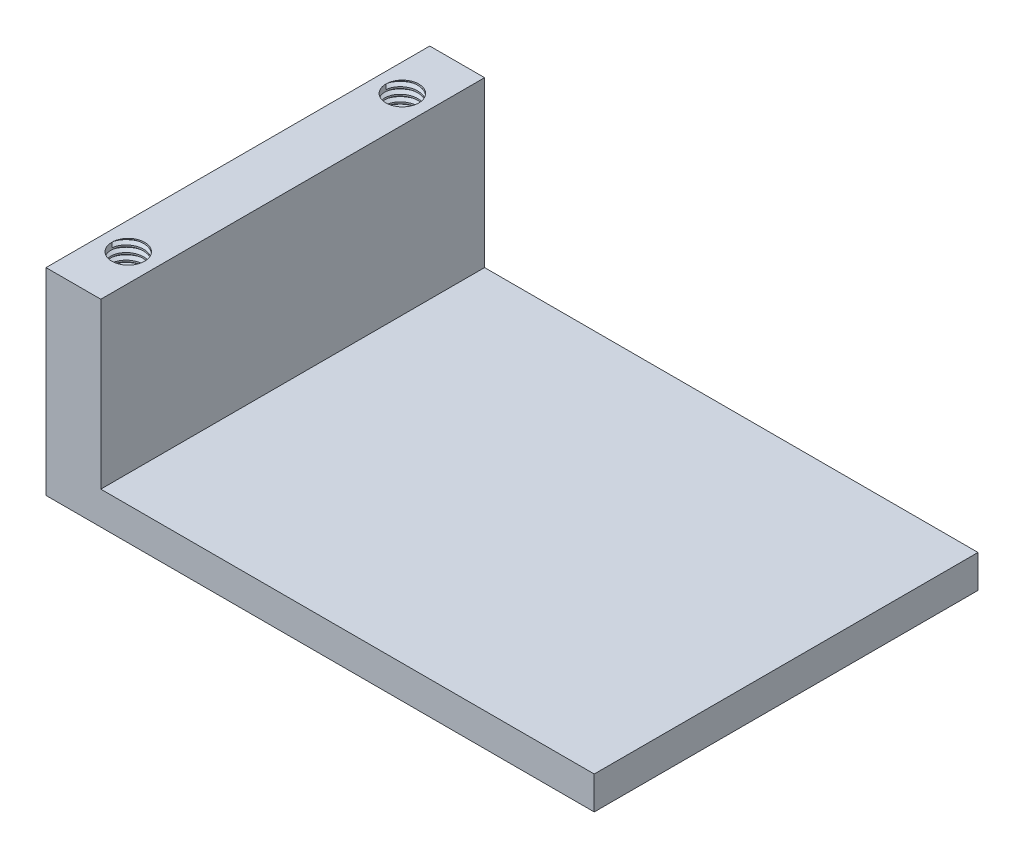
SolidWorks part; units mm, degrees
ref_plane "Front Plane" through (0, 0, 0) normal (0, 0, 1) x (1, 0, 0)
ref_plane "Top Plane" through (0, 0, 0) normal (0, 1, 0) x (1, 0, 0)
ref_plane "Right Plane" through (0, 0, 0) normal (1, 0, 0) x (0, 0, -1)
sketch "Sketch1" plane through (0, 0, 0) normal (0, 0, 1) x (1, 0, 0)
  line L1 (0, 0) -> (4, 0)
  line L2 (0, 0) -> (0, 18)
  line L3 (0, 18) -> (5, 18)
  line L4 (5, 3) -> (5, 18)
  line L5 (4, 0) -> (50, 0)
  line L7 (5, 3) -> (50, 3)
  line L8 (50, 0) -> (50, 3)
  dimension "D1" = 5
  dimension "D2" = 18
  dimension "D3" = 3
  dimension "D4" = 50
extrude "Boss-Extrude1" add sketch "Sketch1" along normal blind 35
sketch "Sketch2" plane through (0, 18, 0) normal (0, 1, 0) x (1, 0, 0)
  circle A0 centre (2.5, -5) radius 1.5
  circle A1 centre (2.5, -30) radius 1.5
extrude "Cut-Extrude1" cut sketch "Sketch2" against normal blind 9
thread "Thread1" pitch 0.6 method cut profile "Thread Profile1" start angle 0, offset 0, length 10, pitch 0.6, diameter 3
ref_plane "Plane1" through (1, 18, 30) normal (0, 0, 1) x (-1, 0, 0)
sketch "Thread Profile1" plane through (1, 18, 30) normal (0, 0, 1) x (-1, 0, 0)
  line L0 (0, 0) -> (0, 0.6) construction
  line L1 (0, 0) -> (0.3248, 0.1875)
  line L2 (0.3248, 0.1875) -> (0.3248, 0.2625)
  line L3 (0.3248, 0.2625) -> (0, 0.45)
  line L4 (0.3248, 0.225) -> (0, 0.225) construction
  line L11 (0, 0) -> (0, 0.45)
  point P2 (0, 0)
  dimension "Pitch" = 0.6
  dimension "Profile_Angle" = 60
  dimension "Profile_Land" = 0.075
  dimension "Profile_Height" = 0.3248
thread "Thread2" pitch 0.6 method cut profile "Thread Profile2" start angle 0, offset 0, length 10, pitch 0.6, diameter 3
ref_plane "Plane2" through (1, 18, 5) normal (0, 0, 1) x (-1, 0, 0)
sketch "Thread Profile2" plane through (1, 18, 5) normal (0, 0, 1) x (-1, 0, 0)
  line L0 (0, 0) -> (0, 0.6) construction
  line L1 (0, 0) -> (0.3248, 0.1875)
  line L2 (0.3248, 0.1875) -> (0.3248, 0.2625)
  line L3 (0.3248, 0.2625) -> (0, 0.45)
  line L4 (0.3248, 0.225) -> (0, 0.225) construction
  line L11 (0, 0) -> (0, 0.45)
  point P2 (0, 0)
  dimension "Pitch" = 0.6
  dimension "Profile_Angle" = 60
  dimension "Profile_Land" = 0.075
  dimension "Profile_Height" = 0.3248
